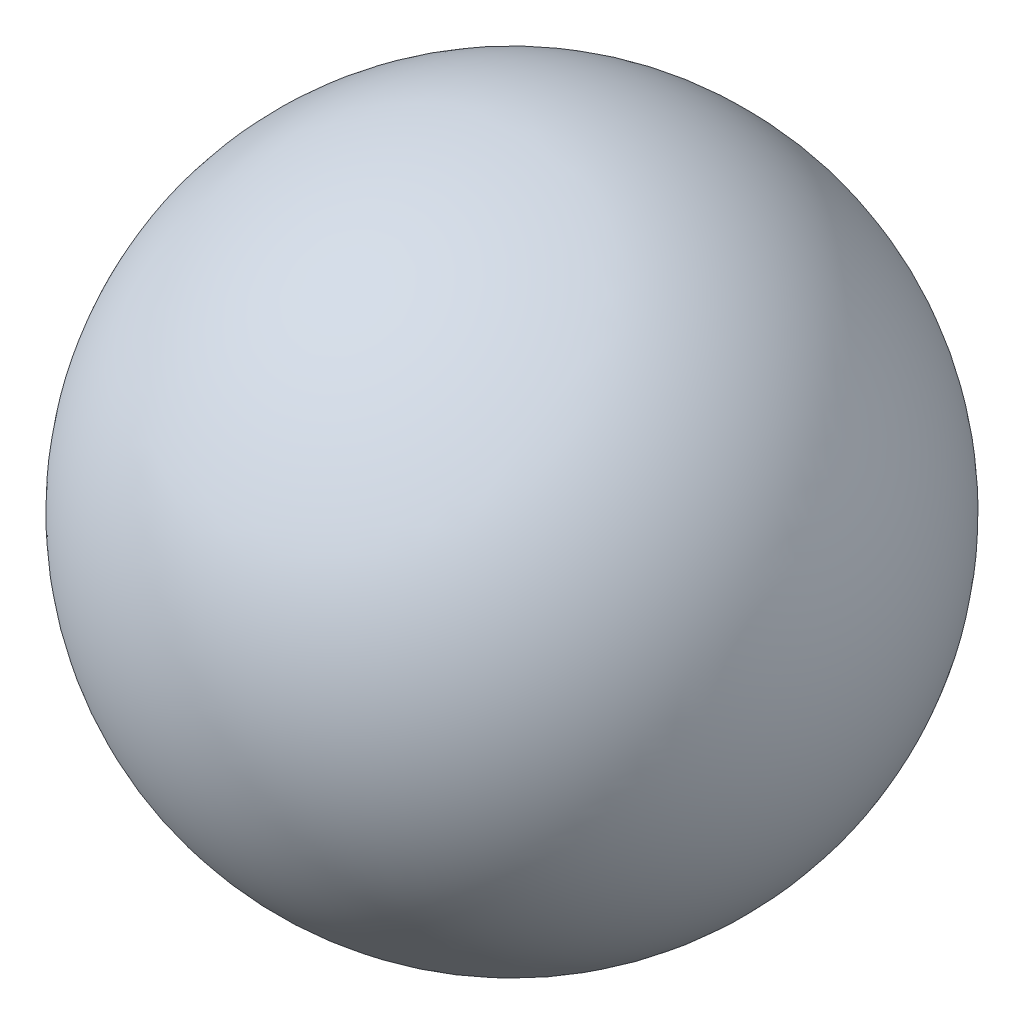
SolidWorks part; units mm, degrees
material "Polyethylene Cross-Linked"
ref_plane "Front Plane" through (0, 0, 0) normal (0, 0, 1) x (1, 0, 0)
ref_plane "Top Plane" through (0, 0, 0) normal (0, 1, 0) x (1, 0, 0)
ref_plane "Right Plane" through (0, 0, 0) normal (1, 0, 0) x (0, 0, -1)
sketch "Sketch3" plane through (0, 0, 0) normal (0, 0, 1) x (1, 0, 0)
  line L0 (0, 0) -> (25.4, 0)
  dimension "D1" = 25.4
sketch "Sketch4" plane through (0, 0, 0) normal (0, 0, 1) x (1, 0, 0)
  line L0 (0, 0) -> (25.4, 0) construction
  line L1 (0, 0) -> (25.4, 0)
  arc A0 (0, 0) -> (25.4, 0) centre (12.7, 0) ccw
revolve "Revolve6" add sketch "Sketch4" angle 360 about L0
